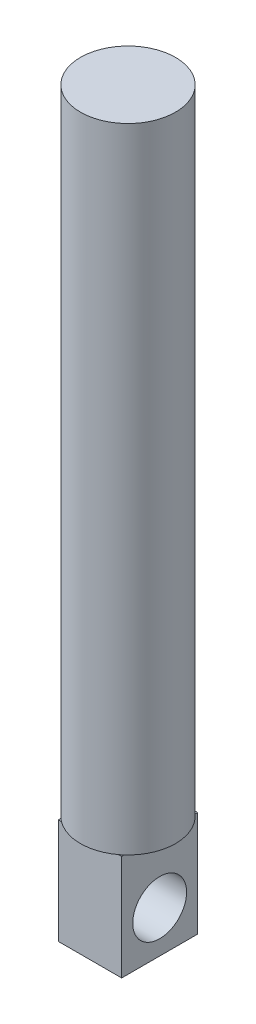
SolidWorks part; units mm, degrees
ref_plane "Front Plane" through (0, 0, 0) normal (0, 0, 1) x (1, 0, 0)
ref_plane "Top Plane" through (0, 0, 0) normal (0, 1, 0) x (1, 0, 0)
ref_plane "Right Plane" through (0, 0, 0) normal (1, 0, 0) x (0, 0, -1)
sketch "Sketch1" plane through (0, 0, 0) normal (0, 1, 0) x (1, 0, 0)
  line L1 (0, 0) -> (5, 0)
  line L2 (0, 0) -> (0, 6)
  line L3 (0, 6) -> (5, 6)
  line L4 (5, 0) -> (5, 6)
  dimension "D1" = 6
  dimension "D2" = 5
extrude "Boss-Extrude1" add sketch "Sketch1" along normal blind 8.31
sketch "Sketch2" plane through (5, 0, 0) normal (1, 0, 0) x (0, 0, -1)
  line L0 (0, 8.31) -> (6, 8.31) construction
  circle A0 centre (3, 3.31) radius 2.125
  dimension "D1" = 5
extrude "Cut-Extrude1" cut sketch "Sketch2" against normal blind 10
sketch "Sketch3" plane through (0, 8.31, 0) normal (0, 1, 0) x (1, 0, 0)
  line L0 (2.5, 0) -> (2.5, 6) construction
  line L1 (0, 0) -> (5, 0) construction
  line L2 (5, 6) -> (0, 6) construction
  line L3 (0, 3) -> (5, 3) construction
  line L4 (0, 6) -> (0, 0) construction
  line L5 (5, 0) -> (5, 6) construction
  circle A0 centre (2.5, 3) radius 3.75
extrude "Boss-Extrude2" add sketch "Sketch3" along normal blind 50
